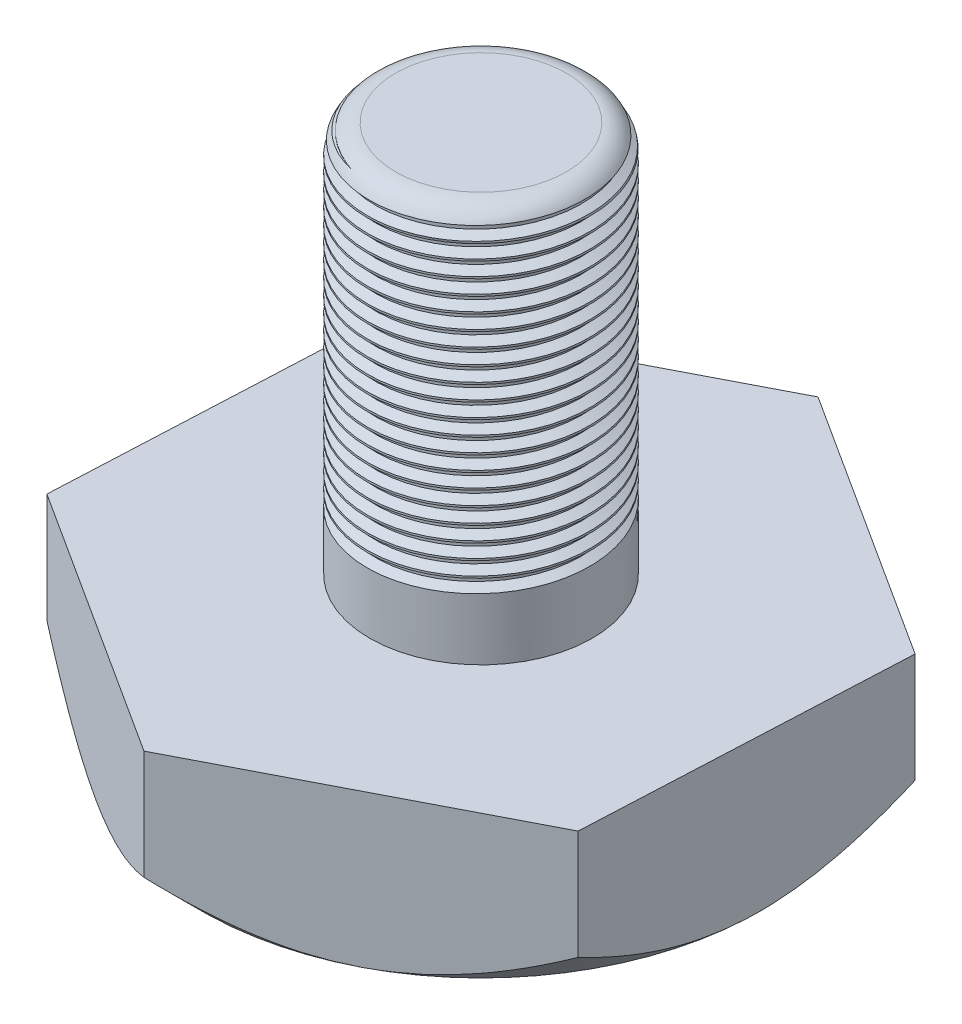
SolidWorks part; units mm, degrees
ref_plane "Front Plane" through (0, 0, 0) normal (0, 0, 1) x (1, 0, 0)
ref_plane "Top Plane" through (0, 0, 0) normal (0, 1, 0) x (1, 0, 0)
ref_plane "Right Plane" through (0, 0, 0) normal (1, 0, 0) x (0, 0, -1)
sketch "Sketch1" plane through (0, 0, 0) normal (0, 1, 0) x (1, 0, 0)
  line L1 (-1.4892, -31.6462) -> (26.6618, -17.1128)
  line L2 (26.6618, -17.1128) -> (28.151, 14.5334)
  line L3 (28.151, 14.5334) -> (1.4892, 31.6462)
  line L4 (1.4892, 31.6462) -> (-26.6618, 17.1128)
  line L5 (-26.6618, 17.1128) -> (-28.151, -14.5334)
  line L6 (-28.151, -14.5334) -> (-1.4892, -31.6462)
  circle A0 centre (0, 0) radius 27.4367 construction
extrude "Boss-Extrude1" add sketch "Sketch1" along normal blind 15
sketch "Sketch4" plane through (0, 15, 0) normal (0, 1, 0) x (1, 0, 0)
  circle A1 centre (0, 0) radius 10.9471
  dimension "D1" = 21.8943
extrude "Boss-Extrude2" add sketch "Sketch4" along normal blind 38.448
fillet "Fillet1" radius 2.54 1 edges at (0, 53.448, 10.9471)
thread "Thread2" pitch 1.5 method cut profile "Thread Profile2" start angle 60, offset 5, length 0, pitch 1.5, diameter 21.8943
ref_plane "Plane2" through (5.4736, 20, -9.4805) normal (0.866, 0, 0.5) x (0.5, 0, -0.866)
sketch "Thread Profile2" plane through (5.4736, 20, -9.4805) normal (0.866, 0, 0.5) x (0.5, 0, -0.866)
  line L0 (0, 0) -> (0, 1.5) construction
  line L11 (0, 0) -> (0, 1.3125)
  line L12 (0, 1.3125) -> (-0.8119, 0.8437)
  line L13 (-0.8119, 0.8437) -> (-0.8119, 0.4687)
  line L15 (-0.8119, 0.4687) -> (0, 0)
  line L17 (-0.8119, 0.6562) -> (0, 0.6562) construction
  point P2 (0, 0)
  dimension "Pitch" = 1.5
  dimension "Profile_Angle" = 60
  dimension "Profile_Land" = 0.375
  dimension "Profile_Height" = 0.8119
sketch "Sketch25" plane through (0, 0, 0) normal (-0.866, 0, -0.5) x (-0.5, 0, 0.866)
  line L4 (-10.9471, 20) -> (-10.1352, 20.4687)
  line L5 (-10.1352, 20.4687) -> (-10.1352, 20.8437)
  line L6 (-10.1352, 20.8437) -> (-10.9471, 21.3125)
  line L7 (-10.9471, 21.3125) -> (-10.9471, 20)
  line L8 (-10.9471, 20) -> (-10.1352, 20.4687)
  line L9 (-10.1352, 20.4687) -> (-10.1352, 20.8437)
  line L10 (-10.1352, 20.8437) -> (-10.9471, 21.3125)
  line L11 (-10.9471, 21.3125) -> (-10.9471, 20)
  dimension "D1" = 0
extrude "Cut-Extrude1" cut sketch "Sketch25" against normal blind 10
sketch "Sketch26" plane through (0, 0, 0) normal (0, -1, 0) x (-1, 0, 0)
  line L0 (26.6618, 17.1128) -> (28.151, -14.5334) construction
  circle A0 centre (0, 0) radius 27.4367
extrude "Cut-Extrude2" cut sketch "Sketch26" against normal through all draft 45 flip side to cut
